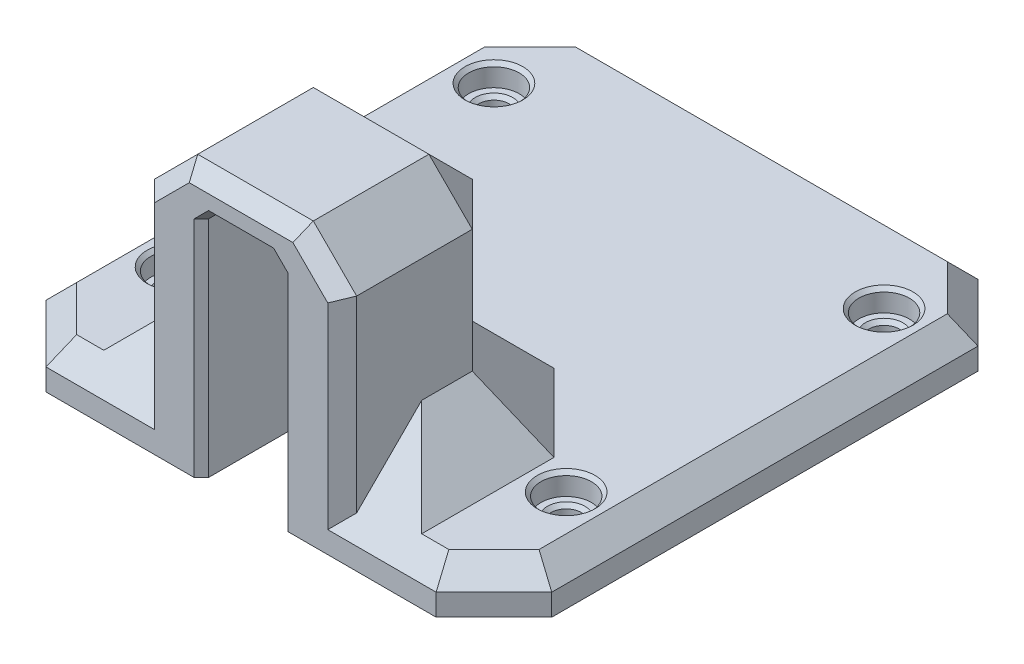
SolidWorks part; units mm, degrees
material "ABS"
ref_plane "Front Plane" through (0, 0, 0) normal (0, 0, 1) x (1, 0, 0)
ref_plane "Top Plane" through (0, 0, 0) normal (0, 1, 0) x (1, 0, 0)
ref_plane "Right Plane" through (0, 0, 0) normal (1, 0, 0) x (0, 0, -1)
sketch "Sketch1" plane through (0, 0, 0) normal (0, 1, 0) x (1, 0, 0)
  line L0 (-35, 27) -> (-27, 35)
  line L1 (-27, 35) -> (27, 35)
  line L2 (-35, 27) -> (-35, -32)
  line L4 (35, 27) -> (35, -32)
  line L5 (27, 35) -> (35, 27)
  line L6 (27, -40) -> (35, -32)
  line L7 (-35, -32) -> (-27, -40)
  line L8 (-1000, 0) -> (49000, 0) construction
  line L9 (0, -1000) -> (0, 49000) construction
  line L11 (-5, -40) -> (-5, -27.65) construction
  line L13 (5, -27.65) -> (5, -40) construction
  line L15 (-5.5, -40) -> (-5.5, -27.8571)
  line L17 (-5.5, -27.8571) -> (-9.5, -23.8571)
  line L18 (-5, -27.65) -> (-9, -23.65) construction
  line L19 (-9, -23.65) -> (-9, -21.15) construction
  line L20 (-9, -21.15) -> (9, -21.15) construction
  line L21 (9, -21.15) -> (9, -23.65) construction
  line L22 (9, -23.65) -> (5, -27.65) construction
  line L23 (-9.5, -23.8571) -> (-9.5, -20.65)
  line L24 (-9.5, -20.65) -> (9.5, -20.65)
  line L25 (9.5, -20.65) -> (9.5, -23.8571)
  line L26 (9.5, -23.8571) -> (5.5, -27.8571)
  line L27 (5.5, -27.8571) -> (5.5, -40)
  line L28 (-27, -40) -> (-5.5, -40)
  line L29 (5.5, -40) -> (27, -40)
  circle A0 centre (-27, 22) radius 2.1
  circle A1 centre (27, 22) radius 2.1
  circle A2 centre (27, -22) radius 2.1
  circle A3 centre (-27, -22) radius 2.1
  point P1 (0, 35)
  point P36 (0, -21.15)
  dimension "D7" = 4.2
  dimension "D1" = 75
  dimension "D2" = 70
  dimension "D3" = 35
  dimension "D4" = 8
  dimension "D5" = 27
  dimension "D6" = 22
  dimension "D8" = 18.85
  dimension "D9" = 18
  dimension "D10" = 4
  dimension "D11" = 2.5
  dimension "D12" = 0.5
extrude "Main Cap Extrude" add sketch "Sketch1" along normal blind 6
chamfer "Main Body Chamfer" distance 3 angle 45 9 edges at (31, 6, 36) (35, 6, 2.5) (31, 6, -31) (0, 6, -35) (-31, 6, -31) (-35, 6, 2.5) (-31, 6, 36) (16.25, 6, 40) (-16.25, 6, 40)
sketch "Sketch4" plane through (0, 6, 0) normal (0, 1, 0) x (1, 0, 0)
  circle A0 centre (-27, 22) radius 3.5
  circle A1 centre (-27, -22) radius 3.5
  circle A2 centre (27, -22) radius 3.5
  circle A3 centre (27, 22) radius 3.5
  dimension "D1" = 7
extrude "Hole Countersink Cut" cut sketch "Sketch4" against normal blind 3
chamfer "Hole Countersink Chamfer" distance 0.5 angle 45 8 edges at (27, 3, -19.9) (27, 3, 24.1) (-27, 3, 24.1) (-27, 3, -19.9) (-27, 6, 25.5) (-27, 6, -18.5) (27, 6, 25.5) (27, 6, -18.5)
sketch "Sketch2" plane through (0, 0, 0) normal (0, 1, 0) x (1, 0, 0)
  line L0 (5.5, -27.8571) -> (5.5, -37) construction
  line L1 (9.5, -23.8571) -> (5.5, -27.8571) construction
  line L2 (9.5, -20.65) -> (9.5, -23.8571) construction
  line L3 (-9.5, -20.65) -> (9.5, -20.65) construction
  line L4 (-9.5, -23.8571) -> (-9.5, -20.65) construction
  line L5 (-5.5, -27.8571) -> (-9.5, -23.8571) construction
  line L6 (-5.5, -37) -> (-5.5, -27.8571) construction
  line L7 (5.5, -27.8571) -> (5.5, -40)
  line L8 (9.5, -23.8571) -> (5.5, -27.8571)
  line L9 (9.5, -20.65) -> (9.5, -23.8571)
  line L10 (-9.5, -20.65) -> (9.5, -20.65)
  line L11 (-9.5, -23.8571) -> (-9.5, -20.65)
  line L12 (-5.5, -27.8571) -> (-9.5, -23.8571)
  line L13 (-5.5, -40) -> (-5.5, -27.8571)
  line L14 (-14, -40) -> (-14, -16)
  line L15 (-27, -40) -> (-5.5, -40) construction
  line L16 (-14, -16) -> (14, -16)
  line L17 (14, -16) -> (14, -40)
  line L18 (5.5, -40) -> (27, -40) construction
  line L19 (14, -40) -> (5.5, -40)
  line L20 (-5.5, -40) -> (-14, -40)
  dimension "D1" = 28
  dimension "D2" = 24
extrude "Main Pinion Chimney Extrude" add sketch "Sketch2" along normal offset from surface (32 mm away) 32 up to face at (0, 0, 15.2955)
sketch "Sketch3" plane through (0, 32, 0) normal (0, 1, 0) x (1, 0, 0)
  line L0 (-14, -16) -> (14, -16)
  line L1 (14, -16) -> (14, -40)
  line L2 (14, -40) -> (-14, -40)
  line L3 (-14, -40) -> (-14, -16)
extrude "Pinion Chimney Cap Extrude" add sketch "Sketch3" along normal blind 5
chamfer "Internal Chimney Chamfer" distance 1 angle 45 10 edges at (9.5, 32, 22.2536) (0, 32, 20.65) (-9.5, 32, 22.2536) (-7.5, 32, 25.8571) (-5.5, 32, 33.9286) (-5.5, 16, 40) (0, 32, 40) (7.5, 32, 25.8571) (5.5, 32, 33.9286) (5.5, 16, 40)
chamfer "Main Chimney External Chamfer" distance 6 angle 45 5 edges at (-14, 37, 28) (14, 37, 28) (-14, 21.5, 16) (14, 21.5, 16) (0, 37, 16)
chamfer "Chimney Plate Chamfer" distance 8 angle 45 5 edges at (14, 6, 29.5) (11, 6, 19) (0, 6, 16) (-11, 6, 19) (-14, 6, 29.5)
chamfer "Chimney Front Chamfer" distance 2 angle 45 5 edges at (14, 17, 40) (11, 34, 40) (0, 37, 40) (-11, 34, 40) (-14, 17, 40)
